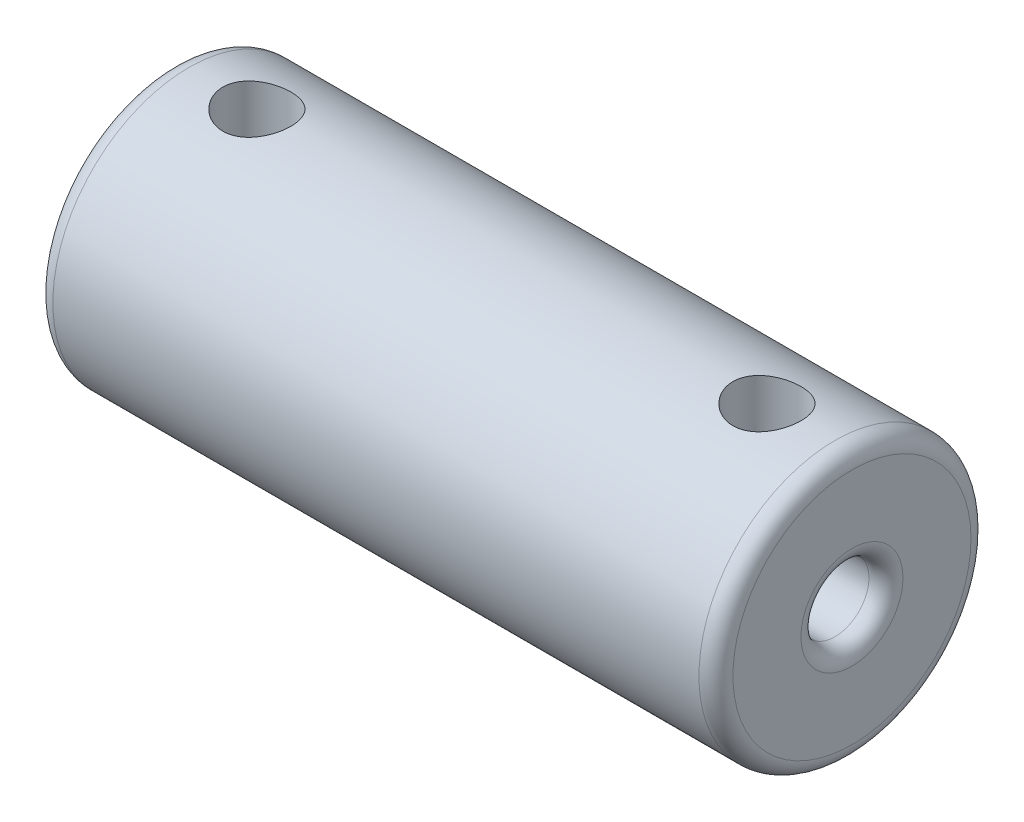
SolidWorks part; units mm, degrees
ref_plane "Front Plane" through (0, 0, 0) normal (0, 0, 1) x (1, 0, 0)
ref_plane "Top Plane" through (0, 0, 0) normal (0, 1, 0) x (1, 0, 0)
ref_plane "Right Plane" through (0, 0, 0) normal (1, 0, 0) x (0, 0, -1)
sketch "Sketch1" plane through (0, 0, 0) normal (1, 0, 0) x (0, 0, -1)
  circle A0 centre (0, 0) radius 4
  dimension "D1" = 8
extrude "Boss-Extrude1" add sketch "Sketch1" along normal blind 10 and the other way blind 10
sketch "Sketch2" plane through (10, 0, 0) normal (1, 0, 0) x (0, 0, -1)
  circle A0 centre (0, 0) radius 1
  dimension "D1" = 2
extrude "Cut-Extrude1" cut sketch "Sketch2" against normal blind 10
sketch "Sketch3" plane through (-10, 0, 0) normal (-1, 0, 0) x (0, 0, 1)
  circle A0 centre (0, 0) radius 2
  dimension "D1" = 4
extrude "Cut-Extrude2" cut sketch "Sketch3" against normal blind 10
sketch "Sketch4" plane through (0, 0, 0) normal (0, 1, 0) x (1, 0, 0)
  line L0 (-10, 0) -> (10, 0) construction
  line L1 (-10, 4) -> (-10, -4) construction
  line L2 (10, -4) -> (10, 4) construction
  circle A0 centre (-7.5, 0) radius 1
  circle A1 centre (7.5, 0) radius 1
  dimension "D3" = 2
  dimension "D4" = 2
  dimension "D1" = 2.5
  dimension "D2" = 2.5
extrude "Cut-Extrude4" cut sketch "Sketch4" along normal up to next
fillet "Fillet1" radius 0.5 4 edges at (10, 0, -1) (10, 0, -4) (-10, 0, -4) (-10, 0, 2)
